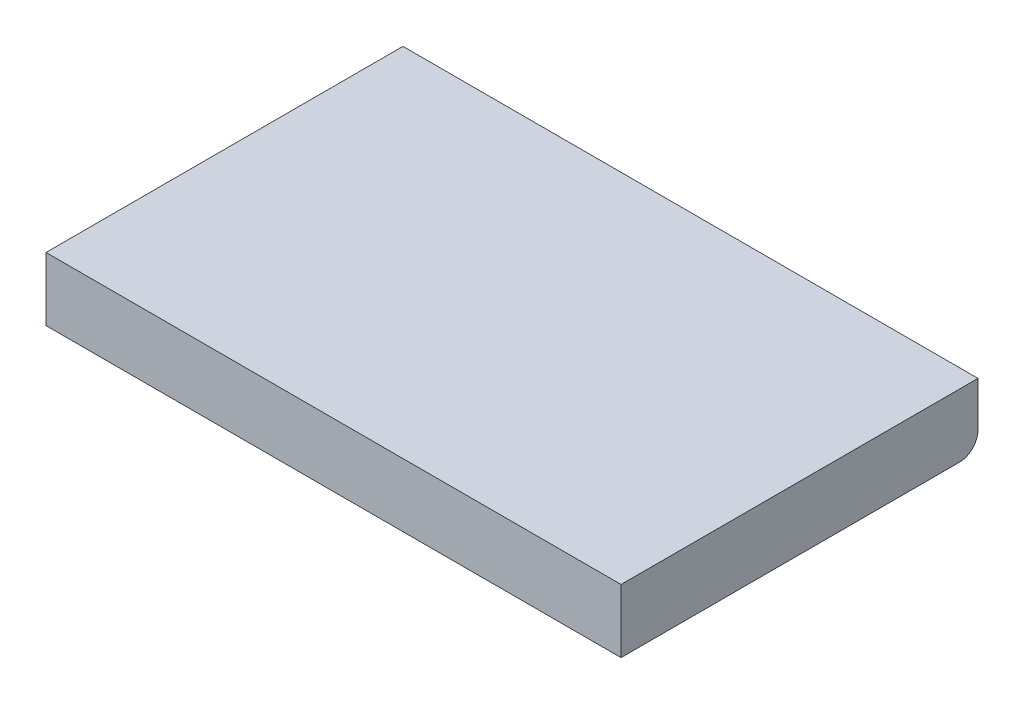
SolidWorks part; units mm, degrees
ref_plane "Front Plane" through (0, 0, 0) normal (0, 0, 1) x (1, 0, 0)
ref_plane "Top Plane" through (0, 0, 0) normal (0, 1, 0) x (1, 0, 0)
ref_plane "Right Plane" through (0, 0, 0) normal (1, 0, 0) x (0, 0, -1)
sketch "Çizim1" plane through (0, 0, 0) normal (0, 1, 0) x (1, 0, 0)
  line L1 (-79.1, 49.1) -> (79.1, 49.1)
  line L2 (-79.1, 49.1) -> (-79.1, -49.1)
  line L3 (-79.1, -49.1) -> (79.1, -49.1)
  line L4 (79.1, 49.1) -> (79.1, -49.1)
  line L5 (-79.1, 49.1) -> (79.1, -49.1) construction
  line L6 (-79.1, -49.1) -> (79.1, 49.1) construction
  point P0 (0, 0)
  dimension "D1" = 158.2
  dimension "D2" = 98.2
extrude "Yükseklik-Ekstrüzyon1" add sketch "Çizim1" along normal blind 6.35
ref_plane "Düzlem1" through (-47.096, 0, 0) normal (1, 0, 0) x (0, 0, -1)
ref_plane "Düzlem2" through (47.096, 0, 0) normal (-1, 0, 0) x (0, 0, 1)
sketch "Çizim2" plane through (-47.096, 0, 0) normal (1, 0, 0) x (0, 0, -1)
  line L0 (49.1, 0) -> (42.75, 0)
  line L1 (49.1, 0) -> (49.1, -2.7997)
  line L2 (42.75, 0) -> (42.75, -2.7997)
  arc A0 (42.75, -2.7997) -> (49.1, -2.7997) centre (45.925, -5.5365) ccw
  dimension "D1" = 6.35
  dimension "D2" = 3.175
extrude "Yükseklik-Ekstrüzyon2" add sketch "Çizim2" along normal blind 34.142
sketch "Çizim3" plane through (47.096, 0, 0) normal (-1, 0, 0) x (0, 0, 1)
  line L0 (-42.75, 0) -> (-49.1, 0)
  line L1 (-42.75, 0) -> (-42.75, -2.7997)
  line L2 (-49.1, 0) -> (-49.1, -2.7997)
  arc A0 (-49.1, -2.7997) -> (-42.75, -2.7997) centre (-45.925, -5.5365) ccw
extrude "Yükseklik-Ekstrüzyon3" add sketch "Çizim3" along normal blind 34.65
sketch "Çizim5" plane through (47.096, 0, 0) normal (1, 0, 0) x (0, 0, -1)
  circle A0 centre (45.925, -5.5365) radius 2.5
extrude "Kes-Ekstrüzyon1" cut sketch "Çizim5" against normal blind 34.142
sketch "Çizim6" plane through (-47.096, 0, 0) normal (-1, 0, 0) x (0, 0, 1)
  circle A0 centre (-45.925, -5.5365) radius 2.5
extrude "Kes-Ekstrüzyon2" cut sketch "Çizim6" against normal blind 34.142
sketch "Çizim7" plane through (-79.1, 0, 0) normal (-1, 0, 0) x (0, 0, 1)
  line L1 (49.1, 0) -> (-49.1, 0)
  line L2 (49.1, 0) -> (49.1, -11.08)
  line L3 (49.1, -11.08) -> (-49.1, -11.08)
  line L4 (-49.1, 0) -> (-49.1, -11.08)
  dimension "D1" = 11.08
extrude "Yükseklik-Ekstrüzyon4" add sketch "Çizim7" against normal blind 6.35
sketch "Çizim10" plane through (79.1, 0, 0) normal (1, 0, 0) x (0, 0, -1)
  line L1 (-49.1, 0) -> (49.1, 0)
  line L2 (-49.1, 0) -> (-49.1, -11.08)
  line L3 (-49.1, -11.08) -> (49.1, -11.08)
  line L4 (49.1, 0) -> (49.1, -11.08)
extrude "Yükseklik-Ekstrüzyon5" add sketch "Çizim10" against normal blind 6.35
sketch "Çizim12" plane through (0, 0, 49.1) normal (0, 0, 1) x (1, 0, 0)
  line L1 (-72.75, 0) -> (72.75, 0)
  line L2 (-72.75, 0) -> (-72.75, -11.08)
  line L3 (-72.75, -11.08) -> (72.75, -11.08)
  line L4 (72.75, 0) -> (72.75, -11.08)
extrude "Yükseklik-Ekstrüzyon6" add sketch "Çizim12" against normal blind 6.35
fillet "Radyus1" radius 5.08 1 edges at (75.925, -11.08, -49.1)
fillet "Radyus2" radius 5.08 1 edges at (-75.925, -11.08, -49.1)
sketch "Çizim15" plane through (-79.1, 0, 0) normal (-1, 0, 0) x (0, 0, 1)
  circle A0 centre (-45.925, -5.5365) radius 2.5
extrude "Kes-Ekstrüzyon3" cut sketch "Çizim15" against normal blind 6.35
